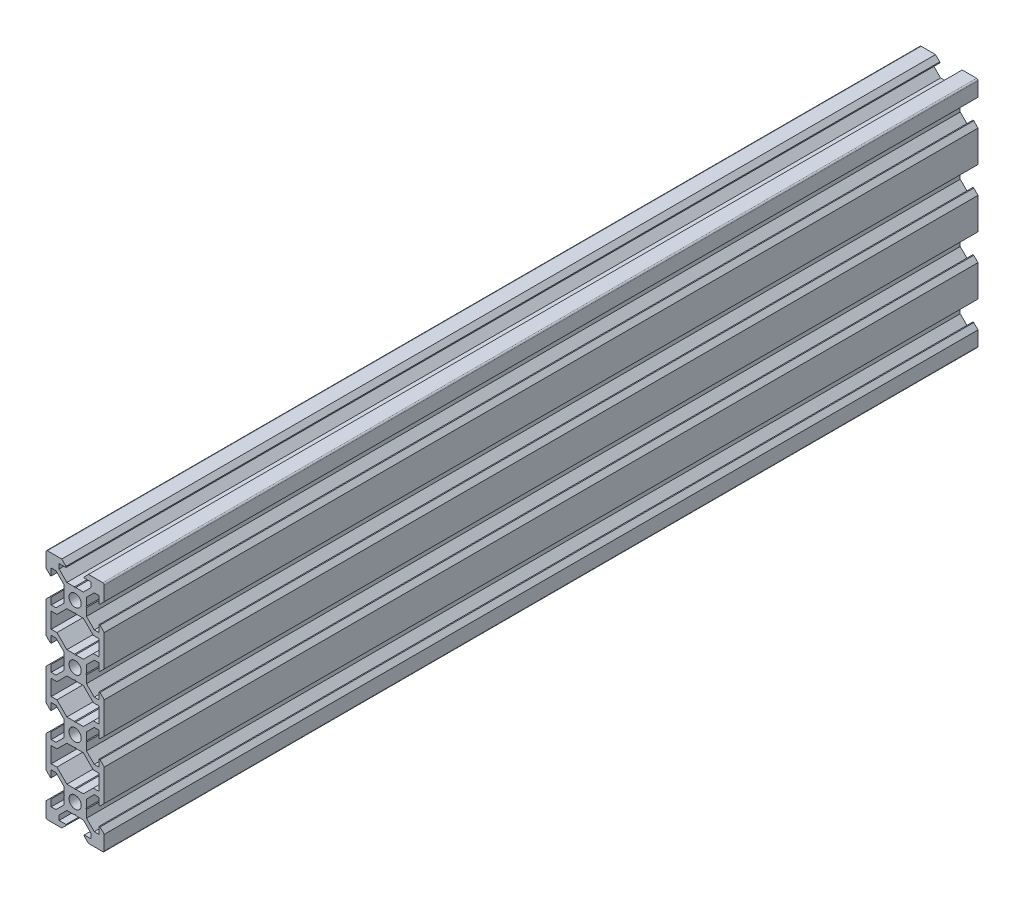
SolidWorks part; units mm, degrees
ref_plane "Plan de face" through (0, 0, 0) normal (0, 0, 1) x (1, 0, 0)
ref_plane "Plan de dessus" through (0, 0, 0) normal (0, 1, 0) x (1, 0, 0)
ref_plane "Plan de droite" through (0, 0, 0) normal (1, 0, 0) x (0, 0, -1)
ref_axis "Axe" through (0, 0, -13.782) along (0, 0, 1)
sketch "Esquisse1" plane through (0, 0, 0) normal (0, 0, 1) x (1, 0, 0)
  line L0 (0, 27.6392) -> (0, -27.6392) construction
  line L1 (-33.6074, 0) -> (33.6074, 0) construction
  line L2 (0, 0) -> (-22.2114, 22.2114) construction
  line L3 (-9.5, 10) -> (-4.58, 10)
  line L4 (-4.58, 10) -> (-3.125, 8.545)
  line L5 (-3.125, 8.545) -> (-3.125, 8.2)
  line L6 (-3.125, 8.2) -> (-5.5, 8.2)
  line L7 (-2.8393, 3.9) -> (-5.5, 6.5607)
  line L8 (-2.8393, 3.9) -> (-0.21, 3.9)
  line L9 (-5.5, 6.5607) -> (-5.5, 8.2)
  line L10 (0, 3.69) -> (0, 2.1)
  line L11 (-3.9, 2.8393) -> (-6.5607, 5.5)
  line L12 (-8.545, 3.125) -> (-8.2, 3.125)
  line L13 (-8.2, 3.125) -> (-8.2, 5.5)
  line L14 (-6.5607, 5.5) -> (-8.2, 5.5)
  line L15 (-10, 4.58) -> (-8.545, 3.125)
  line L16 (-10, 9.5) -> (-10, 4.58)
  line L17 (-0.21, 3.9) -> (0, 3.69)
  line L18 (-3.9, 2.8393) -> (-3.9, 0.21)
  line L19 (-6.2393, -12.7) -> (-8.2, -12.7)
  line L20 (-3.9, 0.21) -> (-3.69, 0)
  line L21 (-0.21, -3.9) -> (0, -3.69)
  line L22 (0, -3.69) -> (0, -2.1)
  line L23 (-6.5607, -5.5) -> (-8.2, -5.5)
  line L24 (-2.8393, -3.9) -> (-0.21, -3.9)
  line L25 (-8.545, -3.125) -> (-8.2, -3.125)
  line L26 (-10, -4.58) -> (-8.545, -3.125)
  line L27 (-8.2, -3.125) -> (-8.2, -5.5)
  line L28 (-2.8393, -3.9) -> (-6.2393, -7.3)
  line L29 (-3.9, -2.8393) -> (-6.5607, -5.5)
  line L30 (-3.9, -2.8393) -> (-3.9, -0.21)
  line L31 (-3.9, -0.21) -> (-3.69, 0)
  line L32 (-6.2393, -7.3) -> (-8.2, -7.3)
  line L33 (-8.2, -7.3) -> (-8.2, -12.7)
  line L34 (-8.2, -10) -> (-10, -10) construction
  line L35 (-10, -15.42) -> (-10, -4.58)
  line L36 (-3.9, -19.79) -> (-3.69, -20)
  line L37 (-3.9, -17.1607) -> (-3.9, -19.79)
  line L38 (-3.9, -17.1607) -> (-6.5607, -14.5)
  line L39 (-2.8393, -16.1) -> (-6.2393, -12.7)
  line L40 (-8.2, -16.875) -> (-8.2, -14.5)
  line L41 (-10, -15.42) -> (-8.545, -16.875)
  line L42 (-8.545, -16.875) -> (-8.2, -16.875)
  line L43 (-2.8393, -16.1) -> (-0.21, -16.1)
  line L44 (-6.5607, -14.5) -> (-8.2, -14.5)
  line L45 (0, -16.31) -> (0, -17.9)
  line L46 (-0.21, -16.1) -> (0, -16.31)
  line L47 (-8.2, -30) -> (-10, -30) construction
  line L48 (-3.69, -20) -> (0, -20) construction
  line L49 (-0.21, -23.9) -> (0, -23.69)
  line L50 (0, -23.69) -> (0, -22.1)
  line L51 (-6.5607, -25.5) -> (-8.2, -25.5)
  line L52 (-2.8393, -23.9) -> (-0.21, -23.9)
  line L53 (-8.545, -23.125) -> (-8.2, -23.125)
  line L54 (-10, -24.58) -> (-8.545, -23.125)
  line L55 (-8.2, -23.125) -> (-8.2, -25.5)
  line L56 (-2.8393, -23.9) -> (-6.2393, -27.3)
  line L57 (-3.9, -22.8393) -> (-6.5607, -25.5)
  line L58 (-3.9, -22.8393) -> (-3.9, -20.21)
  line L59 (-3.9, -20.21) -> (-3.69, -20)
  line L60 (-10, -24.58) -> (-10, -35.42)
  line L61 (-8.2, -32.7) -> (-8.2, -27.3)
  line L62 (-3.69, -40) -> (0, -40) construction
  line L63 (-8.2, -50) -> (-10, -50) construction
  line L64 (0, -60) -> (-22.2114, -82.2114) construction
  line L65 (-33.6074, -60) -> (33.6074, -60) construction
  line L66 (0, -87.6392) -> (0, -32.3608) construction
  line L67 (-6.2393, -32.7) -> (-8.2, -32.7)
  line L68 (-3.9, -39.79) -> (-3.69, -40)
  line L69 (-3.9, -37.1607) -> (-3.9, -39.79)
  line L70 (-3.9, -37.1607) -> (-6.5607, -34.5)
  line L71 (-2.8393, -36.1) -> (-6.2393, -32.7)
  line L72 (-8.2, -36.875) -> (-8.2, -34.5)
  line L73 (-10, -35.42) -> (-8.545, -36.875)
  line L74 (-8.545, -36.875) -> (-8.2, -36.875)
  line L75 (-6.2393, -27.3) -> (-8.2, -27.3)
  line L76 (-2.8393, -36.1) -> (-0.21, -36.1)
  line L77 (-6.5607, -34.5) -> (-8.2, -34.5)
  line L78 (0, -36.31) -> (0, -37.9)
  line L79 (-0.21, -36.1) -> (0, -36.31)
  line L80 (-0.21, -43.9) -> (0, -43.69)
  line L81 (0, -43.69) -> (0, -42.1)
  line L82 (-6.5607, -45.5) -> (-8.2, -45.5)
  line L83 (-2.8393, -43.9) -> (-0.21, -43.9)
  line L84 (-8.545, -43.125) -> (-8.2, -43.125)
  line L85 (-10, -44.58) -> (-8.545, -43.125)
  line L86 (-8.2, -43.125) -> (-8.2, -45.5)
  line L87 (-2.8393, -43.9) -> (-6.2393, -47.3)
  line L88 (-3.9, -42.8393) -> (-6.5607, -45.5)
  line L89 (-3.9, -42.8393) -> (-3.9, -40.21)
  line L90 (-3.9, -40.21) -> (-3.69, -40)
  line L91 (-10, -44.58) -> (-10, -55.42)
  line L92 (-8.2, -52.7) -> (-8.2, -47.3)
  line L93 (-6.2393, -52.7) -> (-8.2, -52.7)
  line L94 (-3.9, -59.79) -> (-3.69, -60)
  line L95 (-3.9, -57.1607) -> (-3.9, -59.79)
  line L96 (-3.9, -57.1607) -> (-6.5607, -54.5)
  line L97 (-2.8393, -56.1) -> (-6.2393, -52.7)
  line L98 (-8.2, -56.875) -> (-8.2, -54.5)
  line L99 (-10, -55.42) -> (-8.545, -56.875)
  line L100 (-8.545, -56.875) -> (-8.2, -56.875)
  line L101 (-2.8393, -56.1) -> (-0.21, -56.1)
  line L102 (-6.5607, -54.5) -> (-8.2, -54.5)
  line L103 (0, -56.31) -> (0, -57.9)
  line L104 (-0.21, -56.1) -> (0, -56.31)
  line L105 (-3.9, -60.21) -> (-3.69, -60)
  line L106 (-6.2393, -47.3) -> (-8.2, -47.3)
  line L107 (-3.9, -62.8393) -> (-3.9, -60.21)
  line L108 (-0.21, -63.9) -> (0, -63.69)
  line L109 (-10, -69.5) -> (-10, -64.58)
  line L110 (-10, -64.58) -> (-8.545, -63.125)
  line L111 (-6.5607, -65.5) -> (-8.2, -65.5)
  line L112 (-8.2, -63.125) -> (-8.2, -65.5)
  line L113 (-8.545, -63.125) -> (-8.2, -63.125)
  line L114 (-3.9, -62.8393) -> (-6.5607, -65.5)
  line L115 (0, -63.69) -> (0, -62.1)
  line L116 (-5.5, -66.5607) -> (-5.5, -68.2)
  line L117 (-2.8393, -63.9) -> (-0.21, -63.9)
  line L118 (-2.8393, -63.9) -> (-5.5, -66.5607)
  line L119 (-3.125, -68.2) -> (-5.5, -68.2)
  line L120 (-3.125, -68.545) -> (-3.125, -68.2)
  line L121 (-4.58, -70) -> (-3.125, -68.545)
  line L122 (-9.5, -70) -> (-4.58, -70)
  arc A0 (0, -2.1) -> (0, 2.1) centre (0, 0) cw
  arc A1 (-9.5, 10) -> (-10, 9.5) centre (-9.5, 9.5) ccw
  arc A2 (0, -42.1) -> (0, -37.9) centre (0, -40) cw
  arc A3 (-9.5, -70) -> (-10, -69.5) centre (-9.5, -69.5) cw
  arc A4 (0, -17.9) -> (0, -22.1) centre (0, -20) ccw
  arc A5 (0, -57.9) -> (0, -62.1) centre (0, -60) ccw
  point P4 (0, 0)
  point P7 (0, 0)
  point P30 (-10, 10)
  point P60 (0, -20)
  point P146 (-10, -70)
  dimension "D5" = 11
  dimension "D2" = 2.1
  dimension "D3" = 6.25
  dimension "D10" = 0.5
  dimension "D4" = 9.16
  dimension "D6" = 1.5
  dimension "D7" = 1.8
  dimension "D8" = 4.3
  dimension "D9" = 20
  dimension "D11" = 0.42
  dimension "D12" = 10
  dimension "D13" = 1.8
extrude "Boss.-Extru.1" add sketch "Esquisse1" along normal blind 300
sketch "Esquisse3" plane through (0, 0, 300) normal (0, 0, 1) x (1, 0, 0)
  line L0 (0, 0) -> (-9.8536, 9.8536) construction
  line L1 (-8.2, 8.2) -> (-8.2, 6.57)
  line L2 (-8.2, 6.57) -> (-7.54, 6.57)
  line L3 (-7.54, 6.57) -> (-6.57, 7.54)
  line L4 (-8.2, 3.125) -> (-8.2, 5.5) construction
  line L5 (-6.57, 8.2) -> (-6.57, 7.54)
  line L6 (-8.2, 8.2) -> (-6.57, 8.2)
  line L7 (-5.5, 6.5607) -> (-5.5, 8.2) construction
  line L8 (-10, -30) -> (6.918, -30) construction
  line L9 (-10, -24.58) -> (-10, -35.42) construction
  line L10 (-8.2, -68.2) -> (-6.57, -68.2)
  line L11 (-6.57, -68.2) -> (-6.57, -67.54)
  line L12 (-7.54, -66.57) -> (-6.57, -67.54)
  line L13 (-8.2, -66.57) -> (-7.54, -66.57)
  line L14 (-8.2, -68.2) -> (-8.2, -66.57)
  arc A0 (-9.5, 10) -> (-10, 9.5) centre (-9.5, 9.5) ccw construction
  point P13 (-7.055, 7.055)
  point P14 (-6.57, 7.87)
  point P26 (-7.055, -67.055)
  dimension "D1" = 1.07
extrude "Enlèv. mat.-Extru.1" [suppressed] cut sketch "Esquisse3" against normal through all
mirror "Symétrie1" of "Enlèv. mat.-Extru.1", "Boss.-Extru.1"
